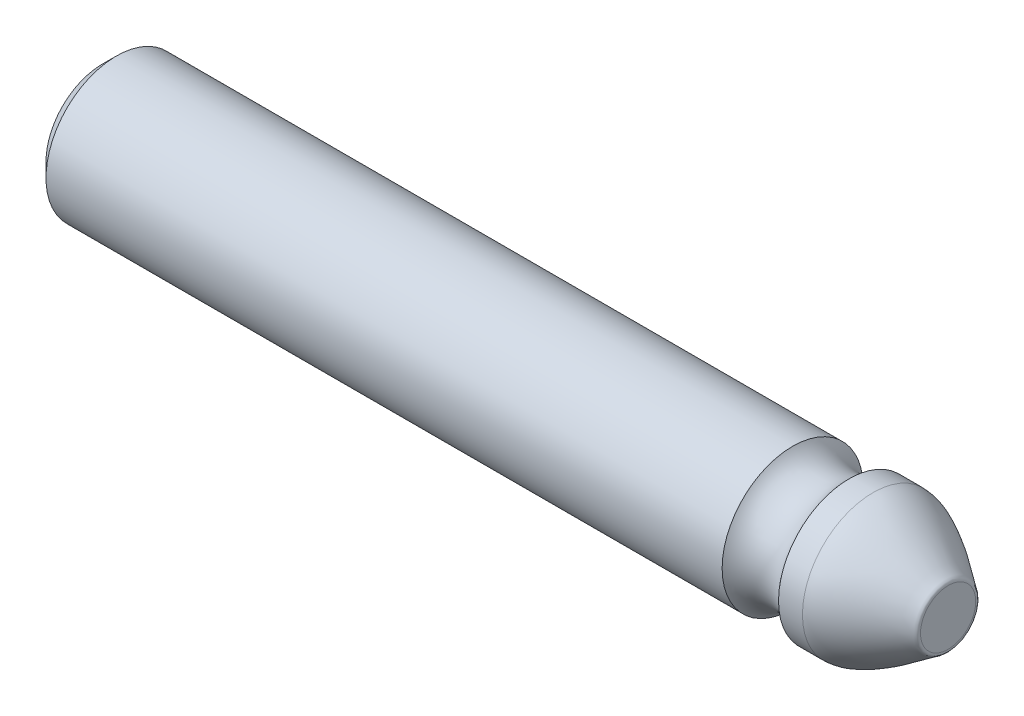
SolidWorks part; units mm, degrees
material "Alloy Steel"
ref_plane "Front" through (0, 0, 0) normal (0, 0, 1) x (1, 0, 0)
ref_plane "Top" through (0, 0, 0) normal (0, 1, 0) x (1, 0, 0)
ref_plane "Right" through (0, 0, 0) normal (1, 0, 0) x (0, 0, -1)
sketch "Sketch1" plane through (0, 0, 0) normal (0, 0, 1) x (1, 0, 0)
  line L0 (-19.05, 0) -> (19.05, 0) construction
  line L1 (19.05, 3.175) -> (19.05, -3.175) construction
  line L2 (-19.05, 3.175) -> (-19.05, -3.175) construction
  dimension "Length" = 38.1
  dimension "Diameter" = 6.35
sketch "Sketch2" plane through (0, 0, 0) normal (1, 0, 0) x (0, 0, -1)
  circle A0 centre (0, 0) radius 3.175
extrude "Extrude1" add sketch "Sketch2" against normal up to vertex (19.05 mm away) and the other way up to vertex (19.05 mm away) up to point (-19.05, 3.175, 0) other way up to point (19.05, 3.175, 0)
chamfer "Chamfer1" distance 0.635 angle 45 2 edges at (19.05, 0, -3.175) (-19.05, 0, -3.175)
sketch "Sketch3" plane through (0, 0, 0) normal (0, 0, 1) x (1, 0, 0)
  line L0 (-19.05, 0) -> (19.05, 0) construction
  line L1 (-19.05, 2.54) -> (-19.05, -2.54) construction
  line L2 (19.05, -2.54) -> (19.05, 2.54) construction
  line L3 (18.415, 3.175) -> (-18.415, 3.175) construction
  line L4 (15.6622, 3.175) -> (14.5842, 3.175)
  line L5 (16.629, 3.175) -> (14.655, 3.175) construction
  line L6 (19.05, 0.802) -> (19.05, 1.6965) construction
  line L7 (19.05, 1.2434) -> (19.05, 3.175)
  line L8 (19.05, 3.175) -> (15.6622, 3.175)
  circle A0 centre (13.3142, 4.1275) radius 1.5875
  spline S0 degree 3 poles (15.6622, 3.175) (16.6428, 3.175) (18.614, 1.6311) (19.0441, 1.3825) (19.05, 1.3487) (19.05, 1.2434) knots 0 0 0 0 0.565725 0.665725 1 1 1 1
  point P16 (0, 0)
  point P19 (18.1654, 1.696)
  point P20 (18.681, 1.2864)
  point P21 (18.8911, 1.471)
  dimension "D1" = 3.175
  dimension "D2" = 0.635
revolve "Cut-Revolve1" cut sketch "Sketch3" angle 360 about L0 region at (13.3142, 4.1275, 0) region at (18.092, 2.592, 0)
equation "\"D1@Chamfer1\" = \"Diameter@Sketch1\"*.1"
